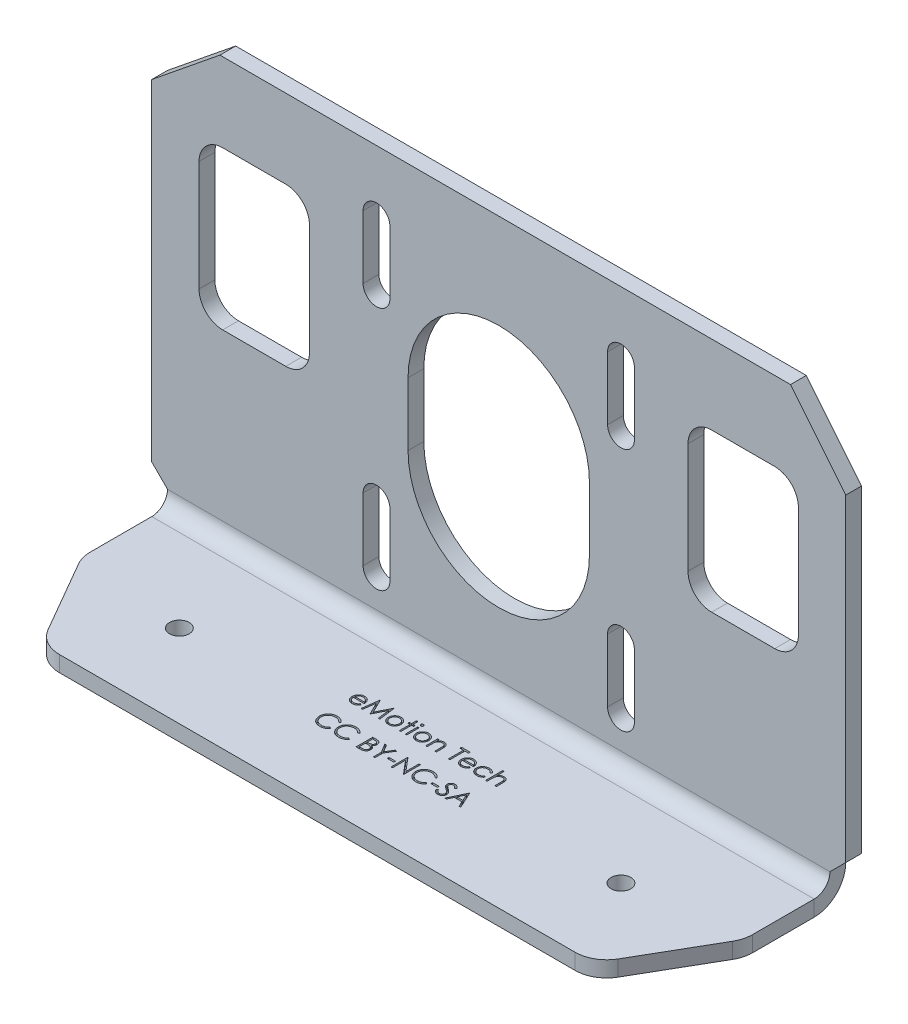
SolidWorks part; units mm, degrees
note: The reader was unsure of these and kept them because the rebuilt part matched: thickness of "Tôle de base pliée1", "Tôle pliée sur arête1", "Tôlerie1", "Tôlerie2", "Tôlerie3", "Tôlerie4", "Tôlerie5"; flange length of "Tôle pliée sur arête1".
material "1023 Tôle d'acier au carbone (SS)"
ref_plane "Plan de face" through (0, 0, 0) normal (0, 0, 1) x (1, 0, 0)
ref_plane "Plan de dessus" through (0, 0, 0) normal (0, 1, 0) x (1, 0, 0)
ref_plane "Plan de droite" through (0, 0, 0) normal (1, 0, 0) x (0, 0, -1)
sketch "Esquisse1" plane through (0, 0, 0) normal (0, 0, 1) x (1, 0, 0)
  line L0 (0, 0) -> (0, 56.0401) construction
  line L1 (-44, 27.5) -> (44, 27.5)
  line L2 (-44, 27.5) -> (-44, -23.5)
  line L3 (-44, -23.5) -> (44, -23.5)
  line L4 (44, 27.5) -> (44, -23.5)
  line L5 (0, 0) -> (73.8199, 0) construction
  dimension "D1" = 88
  dimension "D2" = 51
  dimension "D3" = 44
  dimension "D4" = 27.5
base flange "Tôle de base pliée1" sketch "Esquisse1" thickness 2 reverse thickness direction no parameters "D1"=2
chamfer "Chanfrein3" distance 2 angle 45 2 edges at (44, -23.5, -1) (-44, -23.5, -1)
edge flange "Tôle pliée sur arête1" sketch "Esquisse8" flange angle 90 flange length 25 flange position bend outside bend radius 2 thickness 2 parameters "D6"=10
sketch "Esquisse8" plane through (0, -23.5, 0) normal (0, -1, 0) x (1, 0, 0)
  line L0 (-42, 0) -> (42, 0) construction
  line L1 (-42, 0) -> (42, 0)
  line L2 (-42, 0) -> (-42, 23)
  line L3 (-42, 23) -> (42, 23)
  line L4 (42, 23) -> (42, 0)
bend "Pli d'arête1" bend radius 2 bend angle 90 parameters "D5"=1
sketch "Esquisse9" plane through (0, 0, 0) normal (0, 0, 1) x (1, 0, 0)
  line L0 (0, -4) -> (0, 4) construction
  line L1 (-11.5, -4) -> (-11.5, 4)
  line L2 (11.5, -4) -> (11.5, 4)
  line L3 (-15.5, 19.5) -> (-15.5, 11.5) construction
  line L4 (-13.8, 19.5) -> (-13.8, 11.5)
  line L5 (-17.2, 19.5) -> (-17.2, 11.5)
  line L6 (0, 0) -> (-52.3371, 0) construction
  line L8 (44, 27.5) -> (-44, 27.5) construction
  line L9 (-38, 17.5) -> (-24, 17.5)
  line L10 (-38, 17.5) -> (-38, -2.5)
  line L11 (-38, -2.5) -> (-24, -2.5)
  line L12 (-24, 17.5) -> (-24, -2.5)
  line L13 (-15.5, -19.5) -> (-15.5, -11.5) construction
  line L14 (-13.8, -19.5) -> (-13.8, -11.5)
  line L15 (-17.2, -19.5) -> (-17.2, -11.5)
  line L16 (0, 0) -> (0, 34.9524) construction
  line L17 (38, -2.5) -> (24, -2.5)
  line L18 (38, 17.5) -> (38, -2.5)
  line L19 (38, 17.5) -> (24, 17.5)
  line L20 (24, 17.5) -> (24, -2.5)
  line L21 (15.5, -19.5) -> (15.5, -11.5) construction
  line L22 (13.8, -19.5) -> (13.8, -11.5)
  line L23 (17.2, -19.5) -> (17.2, -11.5)
  line L24 (15.5, 19.5) -> (15.5, 11.5) construction
  line L25 (13.8, 19.5) -> (13.8, 11.5)
  line L26 (17.2, 19.5) -> (17.2, 11.5)
  arc A0 (-11.5, -4) -> (11.5, -4) centre (0, -4) ccw
  arc A1 (11.5, 4) -> (-11.5, 4) centre (0, 4) ccw
  arc A2 (-13.8, 19.5) -> (-17.2, 19.5) centre (-15.5, 19.5) ccw
  arc A3 (-17.2, 11.5) -> (-13.8, 11.5) centre (-15.5, 11.5) ccw
  arc A4 (-13.8, -19.5) -> (-17.2, -19.5) centre (-15.5, -19.5) cw
  arc A5 (-17.2, -11.5) -> (-13.8, -11.5) centre (-15.5, -11.5) cw
  arc A6 (13.8, -19.5) -> (17.2, -19.5) centre (15.5, -19.5) ccw
  arc A7 (17.2, -11.5) -> (13.8, -11.5) centre (15.5, -11.5) ccw
  arc A8 (13.8, 19.5) -> (17.2, 19.5) centre (15.5, 19.5) cw
  arc A9 (17.2, 11.5) -> (13.8, 11.5) centre (15.5, 11.5) cw
  point P3 (0, 0)
  point P8 (-15.5, 15.5)
  point P25 (-15.5, -15.5)
  point P37 (15.5, -15.5)
  point P44 (15.5, 15.5)
  dimension "D4" = 11.5
  dimension "D5" = 1.7
  dimension "D1" = 15.5
  dimension "D2" = 15.5
  dimension "D3" = 8
  dimension "D6" = 10
  dimension "D7" = 14
  dimension "D8" = 20
  dimension "D9" = 24
extrude "Enlèv. mat.-Extru.1" cut sketch "Esquisse9" against normal up to next
fillet "Congé1" radius 3 8 edges at (24, 17.5, -1) (38, 17.5, -1) (38, -2.5, -1) (24, -2.5, -1) (-38, -2.5, -1) (-24, -2.5, -1) (-24, 17.5, -1) (-38, 17.5, -1)
chamfer "Chanfrein1" distance 7 angle 51 2 edges at (44, 27.5, -1) (-44, 27.5, -1)
chamfer "Chanfrein2" distance 7 angle 60 2 edges at (42, -26.5, 23) (-42, -26.5, 23)
fillet "Congé2" radius 4 4 edges at (42, -26.5, 10.8756) (-42, -26.5, 10.8756) (35, -26.5, 23) (-35, -26.5, 23)
hole_wizard "Trou taraudé M31" positions "Esquisse12" profile "Esquisse11" tap size "M3" standard "ISO" end condition through all
sketch "Esquisse12" plane through (0, -27.5, 0) normal (0, -1, 0) x (-1, 0, 0)
  line L0 (0, -23) -> (0, -2) construction
  line L1 (-32.6906, -23) -> (32.6906, -23) construction
  line L2 (-42, -2) -> (42, -2) construction
  line L4 (0, -12.5) -> (-41.0622, -12.5) construction
  line L5 (-41.4641, -11.8038) -> (-36.1547, -21) construction
  point P13 (-28, -12.5)
  point P16 (28, -12.5)
  dimension "D1" = 28
sketch "Esquisse11" plane through (28, -27.5, 12.5) normal (1, 0, 0) x (0, 0, -1)
  line L0 (0, 0) -> (0, 55)
  line L1 (0, 55) -> (1.25, 55)
  line L2 (1.25, 55) -> (1.25, 0)
  line L5 (1.25, 0) -> (0, 0)
  line L11 (0, -6.35) -> (0, 107.95) construction
  dimension "Diamètre du trou pour taraudage jusqu'au prochain" = 2.5
  dimension "Profondeur du trou pour taraudage jusqu'au prochain" = 55
cosmetic thread "Filetage de perçage1"
cosmetic thread "Filetage de perçage2"
sketch "Esquisse13" plane through (0, -25.5, 0) normal (0, 1, 0) x (1, 0, 0)
  line L0 (-42, -9.8038) -> (42, -9.8038) construction
  text T0 "eMotion Tech\r\nCC BY-NC-SA" font "Century Gothic" height in points 8
extrude "Enlèv. mat.-Extru.2" cut sketch "Esquisse13" against normal blind 0.5
sketch "Lignes de pliage1" [suppressed] plane through (0, 0, 0) normal (0, 1, 0) x (1, 0, 0)
sketch "Cube de visualisation1" [suppressed] plane through (0, 0, 0) normal (0, 1, 0) x (1, 0, 0)
sheet metal parameters "Tôlerie1" thickness 2 parameters "D1"=2
flat pattern "Etat déplié1" [suppressed]
sketch "Lignes de pliage2" plane through (0, 0, 0) normal (0, 1, 0) x (1, 0, 0)
sketch3d "Cube de visualisation2" [suppressed]
  line L0 (-43, -29.5, 0) -> (43, -29.5, 0) construction
  line L1 (-43, 27.5, 0) -> (43, 27.5, 0) construction
  line L2 (-43, -29.5, 0) -> (-43, 27.5, 0) construction
  line L3 (43, -29.5, 0) -> (43, 27.5, 0) construction
sheet metal parameters "Tôlerie2" thickness 2 parameters "D1"=2, "D7"=3
flat pattern "Etat déplié1"
sketch "Lignes de pliage2" plane through (0, 0, 0) normal (0, 0, 1) x (1, 0, 0)
  line L0 (-43, -28.0343) -> (43, -28.0343) construction
  line L1 (-43, -28.0343) -> (43, -28.0343) construction
sketch3d "Cube de visualisation2" [suppressed]
  line L0 (-43, -50.5686, 0) -> (43, -50.5686, 0) construction
  line L1 (-43, 27.5, 0) -> (43, 27.5, 0) construction
  line L2 (-43, -50.5686, 0) -> (-43, 27.5, 0) construction
  line L3 (43, -50.5686, 0) -> (43, 27.5, 0) construction
bend of the flat pattern "Dépliage-<Pli d'arête1>1"
sheet metal parameters "Tôlerie3" thickness 2 parameters "D1"=2, "D7"=3
flat pattern "Etat déplié1"
sketch "Lignes de pliage2" plane through (0, 0, 0) normal (0, 0, 1) x (1, 0, 0)
  line L0 (-42, -25.8562) -> (42, -25.8562) construction
  line L1 (-42, -25.8562) -> (42, -25.8562) construction
sketch3d "Cube de visualisation2" [suppressed]
  line L0 (-44, 27.5001, 0) -> (44, 27.5, 0) construction
  line L1 (-44, -49.2123, 0) -> (44, -49.2124, 0) construction
  line L2 (-44, 27.5001, 0) -> (-44, -49.2123, 0) construction
  line L3 (44, 27.5, 0) -> (44, -49.2124, 0) construction
bend of the flat pattern "Dépliage-<Pli d'arête1>1"
sheet metal parameters "Tôlerie4" thickness 2 parameters "D1"=2, "D7"=3
flat pattern "Etat déplié1"
sketch "Lignes de pliage2" plane through (0, 0, 0) normal (0, 0, 1) x (1, 0, 0)
  line L0 (-42, -25.8562) -> (42, -25.8562) construction
  line L1 (-42, -25.8562) -> (42, -25.8562) construction
sketch3d "Cube de visualisation2" [suppressed]
  line L0 (-44, 27.5001, 0) -> (44, 27.5, 0) construction
  line L1 (-44, -49.2123, 0) -> (44, -49.2124, 0) construction
  line L2 (-44, 27.5001, 0) -> (-44, -49.2123, 0) construction
  line L3 (44, 27.5, 0) -> (44, -49.2124, 0) construction
bend of the flat pattern "Dépliage-<Pli d'arête1>1"
sheet metal parameters "Tôlerie5" thickness 2 parameters "D1"=2, "D7"=3
flat pattern "Etat déplié1"
sketch "Lignes de pliage2" plane through (0, 0, 0) normal (0, 0, 1) x (1, 0, 0)
  line L0 (-42, -25.8562) -> (42, -25.8562) construction
  line L1 (-42, -25.8562) -> (42, -25.8562) construction
sketch3d "Cube de visualisation2" [suppressed]
  line L0 (-44, 27.5001, 0) -> (44, 27.5, 0) construction
  line L1 (-44, -49.2123, 0) -> (44, -49.2124, 0) construction
  line L2 (-44, 27.5001, 0) -> (-44, -49.2123, 0) construction
  line L3 (44, 27.5, 0) -> (44, -49.2124, 0) construction
bend of the flat pattern "Dépliage-<Pli d'arête1>1"
